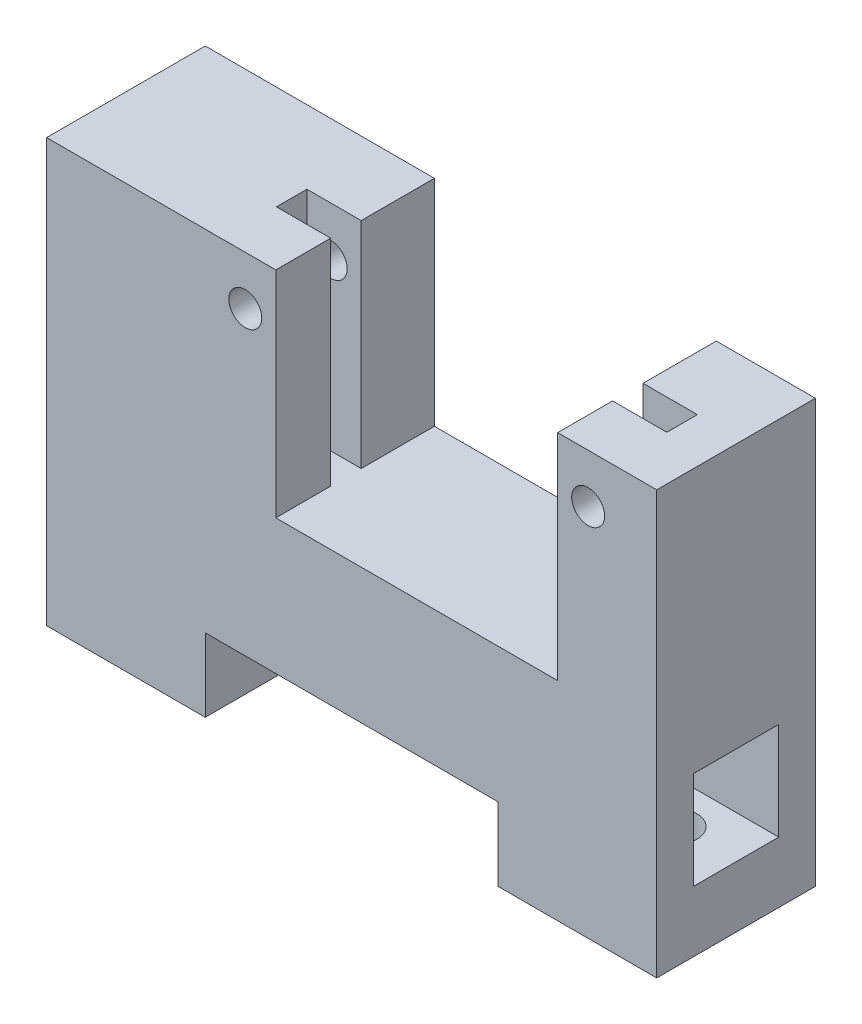
SolidWorks part; units mm, degrees
material "ABS"
ref_plane "Front Plane" through (0, 0, 0) normal (0, 0, 1) x (1, 0, 0)
ref_plane "Top Plane" through (0, 0, 0) normal (0, 1, 0) x (1, 0, 0)
ref_plane "Right Plane" through (0, 0, 0) normal (1, 0, 0) x (0, 0, -1)
sketch "Sketch1" plane through (0, 0, 0) normal (0, 1, 0) x (1, 0, 0)
  line L1 (0, 0) -> (45, 0)
  line L2 (0, 0) -> (0, 6)
  line L3 (0, 6) -> (45, 6)
  line L4 (45, 0) -> (45, 6)
  dimension "D1" = 45
  dimension "D2" = 6
extrude "Boss-Extrude1" add sketch "Sketch1" along normal blind 32
sketch "Sketch2" plane through (0, 0, 0) normal (0, 0, 1) x (1, 0, 0)
  line L0 (0, 32) -> (45, 32) construction
  line L2 (10.95, 32) -> (10.95, 14.4)
  line L3 (10.95, 14.4) -> (34.05, 14.4)
  line L4 (34.05, 32) -> (34.05, 14.4)
  line L5 (10.95, 32) -> (34.05, 32)
  line L6 (22.5, 14.4) -> (22.5, 0) construction
  line L7 (0, 0) -> (45, 0) construction
  dimension "D1" = 23.1
  dimension "D3" = 14.4
extrude "Cut-Extrude1" cut sketch "Sketch2" against normal through all
sketch "Sketch3" plane through (0, 0, 0) normal (0, -1, 0) x (1, 0, 0)
  line L0 (45, 0) -> (45, -6) construction
  line L1 (0, 0) -> (45, 0)
  line L2 (0, 0) -> (0, -20)
  line L3 (0, -20) -> (45, -20)
  line L4 (45, 0) -> (45, -20)
  dimension "D1" = 20
extrude "Boss-Extrude2" add sketch "Sketch3" along normal blind 6
sketch "Sketch4" plane through (45, 0, 0) normal (1, 0, 0) x (0, 0, -1)
  line L1 (20, 0) -> (0, 0)
  line L2 (20, 0) -> (20, -6)
  line L3 (20, -6) -> (0, -6)
  line L4 (0, 0) -> (0, -6)
extrude "Boss-Extrude3" add sketch "Sketch4" along normal blind 30
sketch "Sketch5" plane through (0, -6, 0) normal (0, -1, 0) x (1, 0, 0)
  line L0 (47.2888, -6.75) -> (59.5388, -6.75) construction
  line L1 (37.2888, -16.75) -> (47.2888, -16.75) construction
  line L2 (47.2888, -16.75) -> (59.5388, -16.75) construction
  line L3 (59.5388, -16.75) -> (71.7888, -16.75) construction
  line L4 (71.7888, -16.75) -> (71.7888, -6.75) construction
  line L5 (59.5388, -6.75) -> (59.5388, -16.75) construction
  line L6 (47.2888, -6.75) -> (47.2888, -16.75) construction
  line L7 (0, -20) -> (75, -20) construction
  line L8 (75, 0) -> (75, -20) construction
  line L9 (59.5388, -6.75) -> (71.7888, -6.75) construction
  circle A1 centre (37.2888, -16.75) radius 1.4
  circle A5 centre (47.2888, -16.75) radius 1.4
  circle A7 centre (47.2888, -6.75) radius 1.4
  circle A9 centre (59.5388, -16.75) radius 1.4
  circle A11 centre (71.7888, -16.75) radius 1.4
  circle A13 centre (71.7888, -6.75) radius 1.4
  circle A14 centre (59.5388, -6.75) radius 1.4
  dimension "D1" = 10
  dimension "D2" = 12.25
  dimension "D6" = 2.8
  dimension "D7" = 3.2112
  dimension "D3" = 12.25
  dimension "D4" = 3.25
  dimension "D5" = 10
extrude "Cut-Extrude2" cut sketch "Sketch5" against normal through all
sketch "Sketch6" plane through (0, 0, 0) normal (0, 0, 1) x (1, 0, 0)
  line L0 (0, -6) -> (0, 32)
  line L1 (0, 32) -> (10.95, 32)
  line L2 (10.95, 32) -> (10.95, 14.4)
  line L3 (10.95, 14.4) -> (34.05, 14.4)
  line L4 (34.05, 14.4) -> (34.05, 32)
  line L5 (34.05, 32) -> (45, 32)
  line L6 (45, 32) -> (45, -6)
  line L7 (75, -6) -> (0, -6) construction
  line L8 (45, -6) -> (-0.8534, -6)
  line M1 (45, 32) -> (34.05, 32)
  line M2 (34.05, 32) -> (34.05, 14.4)
  line M3 (34.05, 14.4) -> (10.95, 14.4)
  line M4 (10.95, 14.4) -> (10.95, 32)
  line M5 (10.95, 32) -> (0, 32)
  line M6 (0, 32) -> (0, -6)
  line M7 (0, -6) -> (75, -6)
  line M10 (45, 0) -> (45, 32)
extrude "Boss-Extrude4" add sketch "Sketch6" along normal blind 7 contours L6 M10 M1 M2 M3 M4 M5 M6 M7 region at (22.5, 9.8185, 0)
sketch "Sketch7" plane through (0, 32, 0) normal (0, 1, 0) x (1, 0, 0)
  line L1 (6.5, 0) -> (38.5, 0)
  line L2 (6.5, 0) -> (6.5, -2.5)
  line L3 (6.5, -2.5) -> (38.5, -2.5)
  line L4 (38.5, 0) -> (38.5, -2.5)
  line L5 (22.5, 6) -> (22.5, 0) construction
  line L6 (10.95, 6) -> (34.05, 6) construction
  dimension "D1" = 2.5
  dimension "D2" = 32
extrude "Cut-Extrude3" cut sketch "Sketch7" against normal up to surface (17.6 mm away) up to face at (22.5, 14.4, 0.5)
sketch "Sketch8" plane through (0, 0, 7) normal (0, 0, 1) x (1, 0, 0)
  line L0 (10.95, 32) -> (0, 32) construction
  line L1 (10.95, 14.4) -> (10.95, 32) construction
  line L2 (34.05, 32) -> (34.05, 14.4) construction
  circle A0 centre (8.45, 28) radius 1.35
  circle A1 centre (36.55, 28) radius 1.35
  dimension "D1" = 2.7
  dimension "D3" = 2.5
  dimension "D2" = 4
  dimension "D4" = 2.5
extrude "Cut-Extrude4" cut sketch "Sketch8" against normal through all
chamfer "Chamfer1" distance 1 angle 45 6 edges at (0, -6, -6.5) (37.5, -6, -20) (75, -6, -10) (60, -6, 0) (45, -6, 3.5) (22.5, -6, 7)
fillet "Fillet1" radius 1 3 edges at (22.5, 0, -6) (45, 0, -3) (45, -2.5, 0)
sketch "Sketch9" plane through (0, 0, 7) normal (0, 0, 1) x (1, 0, 0)
  line L0 (0, 32) -> (0, -5) construction
  line L1 (0, 4) -> (75, 4)
  line L2 (0, 4) -> (0, -6)
  line L3 (0, -6) -> (75, -6)
  line L4 (75, 4) -> (75, -6)
  line L5 (75, 0) -> (75, -5) construction
  line L6 (44, -6) -> (1, -6) construction
  point P6 (0, 0)
  dimension "D1" = 10
extrude "Cut-Extrude5" cut sketch "Sketch9" against normal through all
sketch "Sketch10" plane through (0, 4, 0) normal (0, -1, 0) x (1, 0, 0)
  line L4 (45, 7) -> (0, 7)
  line L5 (0, 7) -> (0, -6)
  line L6 (0, -6) -> (45, -6)
  line L7 (45, -6) -> (45, 7)
  line L8 (45, 7) -> (0, 7)
  line L9 (0, 7) -> (0, -6)
  line L10 (0, -6) -> (45, -6)
  line L11 (45, -6) -> (45, 7)
  dimension "D1" = 0
extrude "Boss-Extrude5" add sketch "Sketch10" along normal offset from surface (6.65 mm away) 34.65 up to face at (7.1, 32, 0.875)
sketch "Sketch11" plane through (0, 0, -6) normal (0, 0, -1) x (-1, 0, 0)
  line L0 (0, -2.65) -> (-45, -2.65) construction
  line L1 (-45, 32) -> (-42.17, 32)
  line L2 (-45, 32) -> (-45, -2.65)
  line L3 (-45, -2.65) -> (-42.17, -2.65)
  line L4 (-42.17, 32) -> (-42.17, -2.65)
  dimension "D1" = 2.83
extrude "Cut-Extrude6" cut sketch "Sketch11" against normal through all
sketch "Sketch12" plane through (0, 0, 0) normal (-1, 0, 0) x (0, 0, 1)
  line L4 (-6, 32) -> (-6, -2.65)
  line L5 (-6, -2.65) -> (7, -2.65)
  line L6 (7, -2.65) -> (7, 32)
  line L7 (7, 32) -> (-6, 32)
  line L8 (-6, 32) -> (-6, -2.65)
  line L9 (-6, -2.65) -> (7, -2.65)
  line L10 (7, -2.65) -> (7, 32)
  line L11 (7, 32) -> (-6, 32)
  dimension "D1" = 0
extrude "Boss-Extrude6" add sketch "Sketch12" along normal blind 7.83
sketch "Sketch13" plane through (0, 0, -6) normal (0, 0, -1) x (-1, 0, 0)
  line L0 (7.83, -2.65) -> (-42.17, -2.65) construction
  line L1 (-29.17, -2.65) -> (-5.17, -2.65)
  line L2 (-29.17, -2.65) -> (-29.17, 3.35)
  line L3 (-29.17, 3.35) -> (-5.17, 3.35)
  line L4 (-5.17, -2.65) -> (-5.17, 3.35)
  line L5 (-42.17, -2.65) -> (-42.17, 32) construction
  line L6 (7.83, 32) -> (7.83, -2.65) construction
  dimension "D1" = 13
  dimension "D2" = 13
  dimension "D3" = 6
extrude "Cut-Extrude7" cut sketch "Sketch13" against normal through all
sketch "Sketch14" plane through (42.17, 0, 0) normal (1, 0, 0) x (0, 0, -1)
  line L0 (-7, -2.65) -> (6, -2.65) construction
  line L1 (-4, 10.35) -> (3, 10.35)
  line L2 (-4, 10.35) -> (-4, 2.35)
  line L3 (-4, 2.35) -> (3, 2.35)
  line L4 (3, 10.35) -> (3, 2.35)
  line L5 (-0.5, 2.35) -> (-0.5, -2.65) construction
  dimension "D1" = 7
  dimension "D2" = 8
  dimension "D3" = 5
extrude "Cut-Extrude8" cut sketch "Sketch14" against normal blind 10
sketch "Sketch15" plane through (-7.83, 0, 0) normal (-1, 0, 0) x (0, 0, 1)
  line L5 (4, 2.35) -> (4, 10.35)
  line L6 (-3, 2.35) -> (4, 2.35)
  line L7 (-3, 10.35) -> (-3, 2.35)
  line L8 (4, 10.35) -> (-3, 10.35)
  line L9 (4, 2.35) -> (4, 10.35)
  line L10 (-3, 2.35) -> (4, 2.35)
  line L11 (-3, 10.35) -> (-3, 2.35)
  line L12 (4, 10.35) -> (-3, 10.35)
  dimension "D1" = 0
extrude "Cut-Extrude9" cut sketch "Sketch15" against normal blind 10
sketch "Sketch16" plane through (0, -2.65, 0) normal (0, -1, 0) x (1, 0, 0)
  line L0 (42.17, 4) -> (32.17, -3) construction
  line L1 (-7.83, 4) -> (2.17, -3) construction
hole_wizard "M3 Clearance Hole1" positions "Sketch17" profile "Sketch18" hole size "M3" standard "ANSI Metric" end condition up to next
sketch "Sketch17" plane through (0, -2.65, 0) normal (0, -1, 0) x (-1, 0, 0)
  line L0 (7.83, -4) -> (-2.17, 3) construction
  line L1 (-42.17, -4) -> (-32.17, 3) construction
  point P0 (2.83, -0.5)
  point P4 (-37.17, -0.5)
sketch "Sketch18" plane through (-2.83, -2.65, 0.5) normal (1, 0, 0) x (0, 0, -1)
  line L0 (0, 0) -> (0, 5)
  line L1 (0, 5) -> (1.8, 5)
  line L2 (1.8, 5) -> (1.8, 0)
  line L5 (1.8, 0) -> (0, 0)
  line L11 (0, -6.35) -> (0, 107.95) construction
  dimension "Thru Hole Dia." = 3.6
  dimension "Thru Hole Depth" = 5
